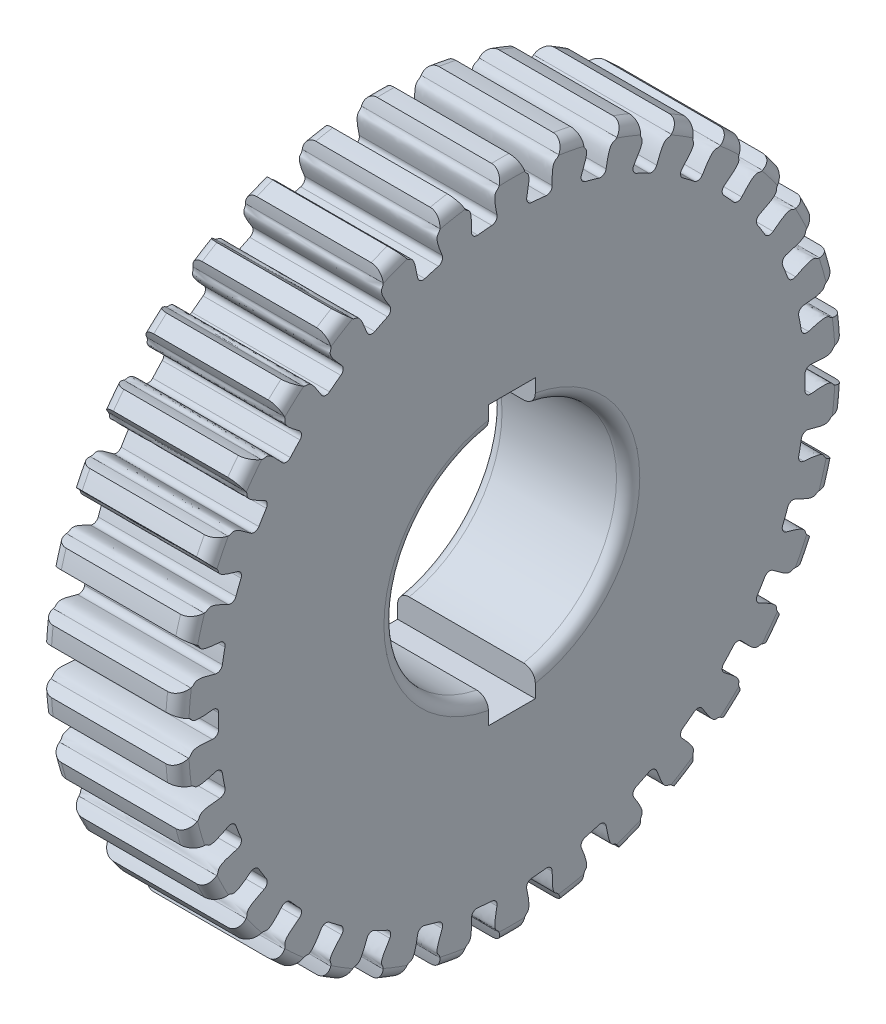
SolidWorks part; units mm, degrees
ref_plane "Front Plane" through (0, 0, 0) normal (0, 0, 1) x (1, 0, 0)
ref_plane "Top Plane" through (0, 0, 0) normal (0, 1, 0) x (1, 0, 0)
ref_plane "Right Plane" through (0, 0, 0) normal (1, 0, 0) x (0, 0, -1)
ref_plane "Plane1" through (4.699, 0, 0) normal (1, 0, 0) x (0, 0, -1)
sketch "Sketch1" plane through (4.699, 0, 0) normal (1, 0, 0) x (0, 0, -1)
  arc A0 (2.7681, 19.8229) -> (0.9216, 19.994) centre (0, 0) ccw
  arc A1 (0.5895, 22.8524) -> (-0.5895, 22.8524) centre (0, 0) ccw
  arc A2 (-0.9214, 19.994) -> (-2.7679, 19.8229) centre (0, 0) ccw
  arc A3 (-3.6196, 22.5716) -> (-4.7786, 22.355) centre (0, 0) ccw
  arc A4 (-4.5796, 19.4842) -> (-6.3632, 18.9768) centre (0, 0) ccw
  arc A5 (-7.7055, 21.5222) -> (-8.805, 21.0963) centre (0, 0) ccw
  arc A6 (-8.0819, 18.311) -> (-9.7419, 17.4844) centre (0, 0) ccw
  arc A7 (-11.529, 19.7398) -> (-12.5315, 19.1192) centre (0, 0) ccw
  arc A8 (-11.3089, 16.5141) -> (-12.7887, 15.3966) centre (0, 0) ccw
  arc A9 (-14.9599, 17.2853) -> (-15.8312, 16.491) centre (0, 0) ccw
  arc A10 (-14.1508, 14.155) -> (-15.4001, 12.7845) centre (0, 0) ccw
  arc A11 (-17.8813, 14.2421) -> (-18.5919, 13.3012) centre (0, 0) ccw
  arc A12 (-16.5108, 11.3137) -> (-17.4871, 9.7371) centre (0, 0) ccw
  arc A13 (-20.1939, 10.7139) -> (-20.7194, 9.6585) centre (0, 0) ccw
  arc A14 (-18.3086, 8.0872) -> (-18.9785, 6.3581) centre (0, 0) ccw
  arc A15 (-21.8187, 6.8209) -> (-22.1414, 5.6868) centre (0, 0) ccw
  arc A16 (-19.4829, 4.5853) -> (-19.8236, 2.7625) centre (0, 0) ccw
  arc A17 (-22.7005, 2.6956) -> (-22.8093, 1.5215) centre (0, 0) ccw
  arc A18 (-19.9937, 0.9273) -> (-19.9937, -0.9271) centre (0, 0) ccw
  arc A19 (-22.8093, -1.5215) -> (-22.7005, -2.6956) centre (0, 0) ccw
  arc A20 (-19.8237, -2.7623) -> (-19.4829, -4.5851) centre (0, 0) ccw
  arc A21 (-22.1414, -5.6868) -> (-21.8187, -6.8209) centre (0, 0) ccw
  arc A22 (-18.9786, -6.3579) -> (-18.3087, -8.0871) centre (0, 0) ccw
  arc A23 (-20.7194, -9.6585) -> (-20.1939, -10.7139) centre (0, 0) ccw
  arc A24 (-17.4872, -9.7369) -> (-16.5109, -11.3136) centre (0, 0) ccw
  arc A25 (-18.5919, -13.3012) -> (-17.8813, -14.2421) centre (0, 0) ccw
  arc A26 (-15.4002, -12.7844) -> (-14.151, -14.1548) centre (0, 0) ccw
  arc A27 (-15.8312, -16.491) -> (-14.9599, -17.2853) centre (0, 0) ccw
  arc A28 (-12.7889, -15.3965) -> (-11.3091, -16.514) centre (0, 0) ccw
  arc A29 (-12.5315, -19.1192) -> (-11.529, -19.7398) centre (0, 0) ccw
  arc A30 (-9.742, -17.4843) -> (-8.0821, -18.3109) centre (0, 0) ccw
  arc A31 (-8.805, -21.0963) -> (-7.7055, -21.5222) centre (0, 0) ccw
  arc A32 (-6.3634, -18.9767) -> (-4.5798, -19.4842) centre (0, 0) ccw
  arc A33 (-4.7786, -22.355) -> (-3.6196, -22.5716) centre (0, 0) ccw
  arc A34 (-2.7681, -19.8229) -> (-0.9216, -19.994) centre (0, 0) ccw
  arc A35 (-0.5895, -22.8524) -> (0.5895, -22.8524) centre (0, 0) ccw
  arc A36 (0.9214, -19.994) -> (2.7679, -19.8229) centre (0, 0) ccw
  arc A37 (3.6196, -22.5716) -> (4.7786, -22.355) centre (0, 0) ccw
  arc A38 (4.5796, -19.4842) -> (6.3632, -18.9768) centre (0, 0) ccw
  arc A39 (7.7055, -21.5222) -> (8.805, -21.0963) centre (0, 0) ccw
  arc A40 (8.0819, -18.311) -> (9.7419, -17.4844) centre (0, 0) ccw
  arc A41 (11.529, -19.7398) -> (12.5315, -19.1192) centre (0, 0) ccw
  arc A42 (11.3089, -16.5141) -> (12.7887, -15.3966) centre (0, 0) ccw
  arc A43 (14.9599, -17.2853) -> (15.8312, -16.491) centre (0, 0) ccw
  arc A44 (14.1508, -14.155) -> (15.4001, -12.7845) centre (0, 0) ccw
  arc A45 (17.8813, -14.2421) -> (18.5919, -13.3012) centre (0, 0) ccw
  arc A46 (16.5108, -11.3137) -> (17.4871, -9.7371) centre (0, 0) ccw
  arc A47 (20.1939, -10.7139) -> (20.7194, -9.6585) centre (0, 0) ccw
  arc A48 (18.3086, -8.0872) -> (18.9785, -6.3581) centre (0, 0) ccw
  arc A49 (21.8187, -6.8209) -> (22.1414, -5.6868) centre (0, 0) ccw
  arc A50 (19.4829, -4.5853) -> (19.8236, -2.7625) centre (0, 0) ccw
  arc A51 (22.7005, -2.6956) -> (22.8093, -1.5215) centre (0, 0) ccw
  arc A52 (19.9937, -0.9273) -> (19.9937, 0.9271) centre (0, 0) ccw
  arc A53 (22.8093, 1.5215) -> (22.7005, 2.6956) centre (0, 0) ccw
  arc A54 (19.8237, 2.7623) -> (19.4829, 4.5851) centre (0, 0) ccw
  arc A55 (22.1414, 5.6868) -> (21.8187, 6.8209) centre (0, 0) ccw
  arc A56 (18.9786, 6.3579) -> (18.3087, 8.0871) centre (0, 0) ccw
  arc A57 (20.7194, 9.6585) -> (20.1939, 10.7139) centre (0, 0) ccw
  arc A58 (17.4872, 9.7369) -> (16.5109, 11.3136) centre (0, 0) ccw
  arc A59 (18.5919, 13.3012) -> (17.8813, 14.2421) centre (0, 0) ccw
  arc A60 (15.4002, 12.7844) -> (14.151, 14.1548) centre (0, 0) ccw
  arc A61 (15.8312, 16.491) -> (14.9599, 17.2853) centre (0, 0) ccw
  arc A62 (12.7889, 15.3965) -> (11.3091, 16.514) centre (0, 0) ccw
  arc A63 (12.5315, 19.1192) -> (11.529, 19.7398) centre (0, 0) ccw
  arc A64 (9.742, 17.4843) -> (8.0821, 18.3109) centre (0, 0) ccw
  arc A65 (8.805, 21.0963) -> (7.7055, 21.5222) centre (0, 0) ccw
  arc A66 (6.3634, 18.9767) -> (4.5798, 19.4842) centre (0, 0) ccw
  arc A67 (4.7786, 22.355) -> (3.6196, 22.5716) centre (0, 0) ccw
  spline S0 degree 3 poles (1.0171, 20.4278) (0.9864, 20.283) (0.9535, 20.1386) (0.9216, 19.994) knots 0 0 0 0 0.000444 0.000444 0.000444 0.000444
  spline S1 degree 3 poles (0.8652, 22.0811) (0.9791, 21.7014) (1.3741, 22.1121) (1.0171, 20.4278) knots 0 0 0 0 1 1 1 1
  spline S2 degree 3 poles (0.8652, 22.0811) (0.8067, 22.2761) (0.74, 22.4689) (0.6667, 22.6589) (0.6417, 22.7237) (0.616, 22.7882) (0.5895, 22.8524) knots 0 0 0 0 0.000611 0.000611 0.000611 0.000819 0.000819 0.000819 0.000819
  spline S3 degree 3 poles (-0.8652, 22.0811) (-0.8118, 22.2592) (-0.7516, 22.4353) (-0.6857, 22.6092) (-0.6549, 22.6908) (-0.6228, 22.7718) (-0.5895, 22.8524) knots 0 0 0 0 0.000558 0.000558 0.000558 0.000819 0.000819 0.000819 0.000819
  spline S4 degree 3 poles (-1.0171, 20.4278) (-1.3741, 22.1121) (-0.9791, 21.7014) (-0.8652, 22.0811) knots 0 0 0 0 1 1 1 1
  spline S5 degree 3 poles (-1.0171, 20.4278) (-0.9864, 20.2829) (-0.9534, 20.1386) (-0.9214, 19.994) knots 0 0 0 0 0.000444 0.000444 0.000444 0.000444
  spline S6 degree 3 poles (-2.7539, 20.2669) (-2.7574, 20.1188) (-2.7632, 19.9709) (-2.7679, 19.8229) knots 0 0 0 0 0.000444 0.000444 0.000444 0.000444
  spline S7 degree 3 poles (-3.2069, 21.8641) (-3.0252, 21.5118) (-2.7124, 21.9881) (-2.7539, 20.2669) knots 0 0 0 0 1 1 1 1
  spline S8 degree 3 poles (-3.2069, 21.8641) (-3.3002, 22.0451) (-3.4012, 22.2223) (-3.5082, 22.3956) (-3.5447, 22.4547) (-3.5818, 22.5134) (-3.6196, 22.5716) knots 0 0 0 0 0.000611 0.000611 0.000611 0.000819 0.000819 0.000819 0.000819
  spline S9 degree 3 poles (-4.9079, 21.5461) (-4.8789, 21.8176) (-4.8345, 22.0877) (-4.7786, 22.355) knots 0.002506 0.002506 0.002506 0.002506 0.003326 0.003326 0.003326 0.003326
  spline S10 degree 3 poles (-4.7533, 19.8931) (-5.4138, 21.4831) (-4.95, 21.152) (-4.9079, 21.5461) knots 0 0 0 0 1 1 1 1
  spline S11 degree 3 poles (-4.7533, 19.8931) (-4.6965, 19.7563) (-4.6376, 19.6205) (-4.5796, 19.4842) knots 0 0 0 0 0.000444 0.000444 0.000444 0.000444
  spline S12 degree 3 poles (-6.431, 19.4158) (-6.4073, 19.2696) (-6.3858, 19.1231) (-6.3632, 18.9768) knots 0 0 0 0 0.000444 0.000444 0.000444 0.000444
  spline S13 degree 3 poles (-7.1698, 20.9025) (-6.9265, 20.5897) (-6.7065, 21.1153) (-6.431, 19.4158) knots 0 0 0 0 1 1 1 1
  spline S14 degree 3 poles (-7.1698, 20.9025) (-7.2947, 21.0632) (-7.4264, 21.2187) (-7.5633, 21.3693) (-7.6101, 21.4208) (-7.6575, 21.4718) (-7.7055, 21.5222) knots 0.001228 0.001228 0.001228 0.001228 0.001836 0.001836 0.001836 0.002044 0.002044 0.002044 0.002044
  spline S15 degree 3 poles (-8.7834, 20.2774) (-8.7979, 20.4626) (-8.8054, 20.6485) (-8.8068, 20.8342) (-8.8075, 20.9216) (-8.8068, 21.0089) (-8.805, 21.0963) knots 0.001119 0.001119 0.001119 0.001119 0.001674 0.001674 0.001674 0.001935 0.001935 0.001935 0.001935
  spline S16 degree 3 poles (-8.3278, 18.681) (-9.2691, 20.1225) (-8.7524, 19.8823) (-8.7834, 20.2774) knots 0 0 0 0 1 1 1 1
  spline S17 degree 3 poles (-8.3278, 18.681) (-8.2468, 18.557) (-8.1639, 18.4343) (-8.0819, 18.311) knots 0 0 0 0 0.000444 0.000444 0.000444 0.000444
  spline S18 degree 3 poles (-9.8891, 17.9035) (-9.839, 17.7642) (-9.7909, 17.6241) (-9.7419, 17.4844) knots 0 0 0 0 0.000444 0.000444 0.000444 0.000444
  spline S19 degree 3 poles (-10.8885, 19.2292) (-10.5919, 18.9664) (-10.4722, 19.5235) (-9.8891, 17.9035) knots 0 0 0 0 1 1 1 1
  spline S20 degree 3 poles (-10.8885, 19.2292) (-11.0409, 19.3642) (-11.1989, 19.4928) (-11.3611, 19.6157) (-11.4166, 19.6577) (-11.4726, 19.6991) (-11.529, 19.7398) knots 0.001228 0.001228 0.001228 0.001228 0.001836 0.001836 0.001836 0.002044 0.002044 0.002044 0.002044
  spline S21 degree 3 poles (-12.3598, 18.3182) (-12.4081, 18.4976) (-12.4496, 18.6789) (-12.4851, 18.8612) (-12.5018, 18.947) (-12.5173, 19.033) (-12.5315, 19.1192) knots 0.001119 0.001119 0.001119 0.001119 0.001674 0.001674 0.001674 0.001935 0.001935 0.001935 0.001935
  spline S22 degree 3 poles (-11.6186, 16.8327) (-12.8088, 18.0767) (-12.2568, 17.9355) (-12.3598, 18.3182) knots 0 0 0 0 1 1 1 1
  spline S23 degree 3 poles (-11.6186, 16.8327) (-11.5162, 16.7257) (-11.4122, 16.6203) (-11.3089, 16.5141) knots 0 0 0 0 0.000444 0.000444 0.000444 0.000444
  spline S24 degree 3 poles (-13.0105, 15.7815) (-12.9356, 15.6538) (-12.8626, 15.525) (-12.7887, 15.3966) knots 0 0 0 0 0.000444 0.000444 0.000444 0.000444
  spline S25 degree 3 poles (-14.2365, 16.901) (-13.8966, 16.6972) (-13.8814, 17.2668) (-13.0105, 15.7815) knots 0 0 0 0 1 1 1 1
  spline S26 degree 3 poles (-14.2365, 16.901) (-14.411, 17.0057) (-14.59, 17.1031) (-14.7721, 17.1941) (-14.8343, 17.2252) (-14.8969, 17.2556) (-14.9599, 17.2853) knots 0.001228 0.001228 0.001228 0.001228 0.001836 0.001836 0.001836 0.002044 0.002044 0.002044 0.002044
  spline S27 degree 3 poles (-15.5153, 15.7352) (-15.5958, 15.9026) (-15.6699, 16.0733) (-15.7383, 16.246) (-15.7705, 16.3272) (-15.8014, 16.4089) (-15.8312, 16.491) knots 0.001119 0.001119 0.001119 0.001119 0.001674 0.001674 0.001674 0.001935 0.001935 0.001935 0.001935
  spline S28 degree 3 poles (-14.5137, 14.4111) (-15.9123, 15.4153) (-15.3437, 15.378) (-15.5153, 15.7352) knots 0 0 0 0 1 1 1 1
  spline S29 degree 3 poles (-14.5137, 14.4111) (-14.3935, 14.3248) (-14.2718, 14.2403) (-14.1508, 14.155) knots 0 0 0 0 0.000444 0.000444 0.000444 0.000444
  spline S30 degree 3 poles (-15.6888, 13.1221) (-15.5917, 13.0103) (-15.4963, 12.8971) (-15.4001, 12.7845) knots 0 0 0 0 0.000444 0.000444 0.000444 0.000444
  spline S31 degree 3 poles (-17.0996, 13.9973) (-16.7281, 13.8594) (-16.8178, 14.4221) (-15.6888, 13.1221) knots 0 0 0 0 1 1 1 1
  spline S32 degree 3 poles (-17.0996, 13.9973) (-17.2904, 14.0681) (-17.4843, 14.131) (-17.6799, 14.187) (-17.7469, 14.2061) (-17.814, 14.2245) (-17.8813, 14.2421) knots 0.001228 0.001228 0.001228 0.001228 0.001836 0.001836 0.001836 0.002044 0.002044 0.002044 0.002044
  spline S33 degree 3 poles (-18.1425, 12.6163) (-18.2523, 12.7661) (-18.3565, 12.9202) (-18.4555, 13.0774) (-18.5021, 13.1513) (-18.5475, 13.226) (-18.5919, 13.3012) knots 0.001119 0.001119 0.001119 0.001119 0.001674 0.001674 0.001674 0.001935 0.001935 0.001935 0.001935
  spline S34 degree 3 poles (-16.9147, 11.4989) (-18.4739, 12.229) (-17.9081, 12.2967) (-18.1425, 12.6163) knots 0 0 0 0 1 1 1 1
  spline S35 degree 3 poles (-16.9147, 11.4989) (-16.7805, 11.4361) (-16.6455, 11.3754) (-16.5108, 11.3137) knots 0 0 0 0 0.000444 0.000444 0.000444 0.000444
  spline S36 degree 3 poles (-17.8329, 10.0159) (-17.7169, 9.9238) (-17.6023, 9.8301) (-17.4871, 9.7371) knots 0 0 0 0 0.000444 0.000444 0.000444 0.000444
  spline S37 degree 3 poles (-19.3805, 10.6169) (-18.9899, 10.5496) (-19.1815, 11.0863) (-17.8329, 10.0159) knots 0 0 0 0 1 1 1 1
  spline S38 degree 3 poles (-19.3805, 10.6169) (-19.581, 10.6515) (-19.7832, 10.6777) (-19.9858, 10.6967) (-20.0551, 10.7033) (-20.1244, 10.709) (-20.1939, 10.7139) knots 0.001228 0.001228 0.001228 0.001228 0.001836 0.001836 0.001836 0.002044 0.002044 0.002044 0.002044
  spline S39 degree 3 poles (-20.1518, 9.0678) (-20.2873, 9.1949) (-20.418, 9.3273) (-20.5442, 9.4636) (-20.6036, 9.5277) (-20.662, 9.5927) (-20.7194, 9.6585) knots 0.001119 0.001119 0.001119 0.001119 0.001674 0.001674 0.001674 0.001935 0.001935 0.001935 0.001935
  spline S40 degree 3 poles (-18.7396, 8.195) (-20.4064, 8.6262) (-19.8627, 8.7967) (-20.1518, 9.0678) knots 0 0 0 0 1 1 1 1
  spline S41 degree 3 poles (-18.7396, 8.195) (-18.5962, 8.1579) (-18.4523, 8.1231) (-18.3086, 8.0872) knots 0 0 0 0 0.000444 0.000444 0.000444 0.000444
  spline S42 degree 3 poles (-19.3697, 6.5686) (-19.2387, 6.4994) (-19.1088, 6.4283) (-18.9785, 6.3581) knots 0 0 0 0 0.000444 0.000444 0.000444 0.000444
  spline S43 degree 3 poles (-21.0013, 6.875) (-20.6051, 6.8806) (-20.892, 7.3729) (-19.3697, 6.5686) knots 0 0 0 0 1 1 1 1
  spline S44 degree 3 poles (-21.0013, 6.875) (-21.2048, 6.8721) (-21.4083, 6.8607) (-21.611, 6.8422) (-21.6803, 6.8359) (-21.7495, 6.8288) (-21.8187, 6.8209) knots 0.001228 0.001228 0.001228 0.001228 0.001836 0.001836 0.001836 0.002044 0.002044 0.002044 0.002044
  spline S45 degree 3 poles (-21.4749, 5.2106) (-21.6315, 5.3106) (-21.7843, 5.4166) (-21.9334, 5.5274) (-22.0035, 5.5795) (-22.0728, 5.6327) (-22.1414, 5.6868) knots 0.001119 0.001119 0.001119 0.001119 0.001674 0.001674 0.001674 0.001935 0.001935 0.001935 0.001935
  spline S46 degree 3 poles (-19.9263, 4.6121) (-21.644, 4.7296) (-21.1409, 4.9972) (-21.4749, 5.2106) knots 0 0 0 0 1 1 1 1
  spline S47 degree 3 poles (-19.9263, 4.6121) (-19.7786, 4.602) (-19.6307, 4.5942) (-19.4829, 4.5853) knots 0 0 0 0 0.000444 0.000444 0.000444 0.000444
  spline S48 degree 3 poles (-20.2468, 2.8976) (-20.1054, 2.8536) (-19.9647, 2.8076) (-19.8236, 2.7625) knots 0 0 0 0 0.000444 0.000444 0.000444 0.000444
  spline S49 degree 3 poles (-21.907, 2.8989) (-21.5185, 2.9773) (-21.891, 3.4085) (-20.2468, 2.8976) knots 0 0 0 0 1 1 1 1
  spline S50 degree 3 poles (-21.907, 2.8989) (-22.1067, 2.8587) (-22.3048, 2.81) (-22.5008, 2.7546) (-22.5676, 2.7357) (-22.6342, 2.716) (-22.7005, 2.6956) knots 0 0 0 0 0.000611 0.000611 0.000611 0.000819 0.000819 0.000819 0.000819
  spline S51 degree 3 poles (-22.0667, 1.1758) (-22.2391, 1.2454) (-22.409, 1.3217) (-22.5761, 1.4033) (-22.6544, 1.4416) (-22.7321, 1.481) (-22.8093, 1.5215) knots 0 0 0 0 0.000558 0.000558 0.000558 0.000819 0.000819 0.000819 0.000819
  spline S52 degree 3 poles (-20.4345, 0.8721) (-22.1446, 0.672) (-21.6992, 1.0275) (-22.0667, 1.1758) knots 0 0 0 0 1 1 1 1
  spline S53 degree 3 poles (-20.4345, 0.8721) (-20.2874, 0.8893) (-20.1406, 0.9088) (-19.9937, 0.9273) knots 0 0 0 0 0.000444 0.000444 0.000444 0.000444
  spline S54 degree 3 poles (-20.4345, -0.8721) (-20.2874, -0.8893) (-20.1406, -0.9087) (-19.9937, -0.9271) knots 0 0 0 0 0.000444 0.000444 0.000444 0.000444
  spline S55 degree 3 poles (-22.0667, -1.1758) (-21.6992, -1.0275) (-22.1446, -0.672) (-20.4345, -0.8721) knots 0 0 0 0 1 1 1 1
  spline S56 degree 3 poles (-22.0667, -1.1758) (-22.2556, -1.2521) (-22.4413, -1.3363) (-22.6238, -1.4268) (-22.686, -1.4577) (-22.7478, -1.4893) (-22.8093, -1.5215) knots 0 0 0 0 0.000611 0.000611 0.000611 0.000819 0.000819 0.000819 0.000819
  spline S57 degree 3 poles (-21.907, -2.8989) (-22.1747, -2.845) (-22.4396, -2.7759) (-22.7005, -2.6956) knots 0.002506 0.002506 0.002506 0.002506 0.003326 0.003326 0.003326 0.003326
  spline S58 degree 3 poles (-20.2468, -2.8976) (-21.891, -3.4085) (-21.5185, -2.9773) (-21.907, -2.8989) knots 0 0 0 0 1 1 1 1
  spline S59 degree 3 poles (-20.2468, -2.8976) (-20.1054, -2.8536) (-19.9647, -2.8075) (-19.8237, -2.7623) knots 0 0 0 0 0.000444 0.000444 0.000444 0.000444
  spline S60 degree 3 poles (-19.9263, -4.6121) (-19.7786, -4.602) (-19.6307, -4.5941) (-19.4829, -4.5851) knots 0 0 0 0 0.000444 0.000444 0.000444 0.000444
  spline S61 degree 3 poles (-21.4749, -5.2106) (-21.1409, -4.9972) (-21.644, -4.7296) (-19.9263, -4.6121) knots 0 0 0 0 1 1 1 1
  spline S62 degree 3 poles (-21.4749, -5.2106) (-21.6464, -5.3201) (-21.8134, -5.4369) (-21.976, -5.5593) (-22.0316, -5.6012) (-22.0867, -5.6437) (-22.1414, -5.6868) knots 0.001228 0.001228 0.001228 0.001228 0.001836 0.001836 0.001836 0.002044 0.002044 0.002044 0.002044
  spline S63 degree 3 poles (-21.0013, -6.875) (-21.1871, -6.8724) (-21.3728, -6.8626) (-21.5579, -6.8469) (-21.645, -6.8395) (-21.7319, -6.8308) (-21.8187, -6.8209) knots 0.001119 0.001119 0.001119 0.001119 0.001674 0.001674 0.001674 0.001935 0.001935 0.001935 0.001935
  spline S64 degree 3 poles (-19.3697, -6.5686) (-20.892, -7.3729) (-20.6051, -6.8806) (-21.0013, -6.875) knots 0 0 0 0 1 1 1 1
  spline S65 degree 3 poles (-19.3697, -6.5686) (-19.2387, -6.4994) (-19.1089, -6.4282) (-18.9786, -6.3579) knots 0 0 0 0 0.000444 0.000444 0.000444 0.000444
  spline S66 degree 3 poles (-18.7396, -8.195) (-18.5962, -8.1579) (-18.4523, -8.123) (-18.3087, -8.0871) knots 0 0 0 0 0.000444 0.000444 0.000444 0.000444
  spline S67 degree 3 poles (-20.1518, -9.0678) (-19.8627, -8.7967) (-20.4064, -8.6262) (-18.7396, -8.195) knots 0 0 0 0 1 1 1 1
  spline S68 degree 3 poles (-20.1518, -9.0678) (-20.3003, -9.2071) (-20.443, -9.3526) (-20.5803, -9.5028) (-20.6273, -9.5541) (-20.6736, -9.606) (-20.7194, -9.6585) knots 0.001228 0.001228 0.001228 0.001228 0.001836 0.001836 0.001836 0.002044 0.002044 0.002044 0.002044
  spline S69 degree 3 poles (-19.3805, -10.6169) (-19.5636, -10.6485) (-19.7479, -10.673) (-19.9328, -10.6916) (-20.0197, -10.7003) (-20.1067, -10.7077) (-20.1939, -10.7139) knots 0.001119 0.001119 0.001119 0.001119 0.001674 0.001674 0.001674 0.001935 0.001935 0.001935 0.001935
  spline S70 degree 3 poles (-17.8329, -10.0159) (-19.1815, -11.0863) (-18.9899, -10.5496) (-19.3805, -10.6169) knots 0 0 0 0 1 1 1 1
  spline S71 degree 3 poles (-17.8329, -10.0159) (-17.7169, -9.9238) (-17.6023, -9.83) (-17.4872, -9.7369) knots 0 0 0 0 0.000444 0.000444 0.000444 0.000444
  spline S72 degree 3 poles (-16.9147, -11.4989) (-16.7806, -11.4361) (-16.6455, -11.3753) (-16.5109, -11.3136) knots 0 0 0 0 0.000444 0.000444 0.000444 0.000444
  spline S73 degree 3 poles (-18.1425, -12.6163) (-17.9081, -12.2967) (-18.4739, -12.229) (-16.9147, -11.4989) knots 0 0 0 0 1 1 1 1
  spline S74 degree 3 poles (-18.1425, -12.6163) (-18.2628, -12.7804) (-18.3763, -12.9497) (-18.4837, -13.1226) (-18.5205, -13.1817) (-18.5565, -13.2412) (-18.5919, -13.3012) knots 0.001228 0.001228 0.001228 0.001228 0.001836 0.001836 0.001836 0.002044 0.002044 0.002044 0.002044
  spline S75 degree 3 poles (-17.0996, -13.9973) (-17.2738, -14.0619) (-17.4505, -14.12) (-17.6288, -14.1722) (-17.7126, -14.1967) (-17.7968, -14.22) (-17.8813, -14.2421) knots 0.001119 0.001119 0.001119 0.001119 0.001674 0.001674 0.001674 0.001935 0.001935 0.001935 0.001935
  spline S76 degree 3 poles (-15.6888, -13.1221) (-16.8178, -14.4221) (-16.7281, -13.8594) (-17.0996, -13.9973) knots 0 0 0 0 1 1 1 1
  spline S77 degree 3 poles (-15.6888, -13.1221) (-15.5917, -13.0103) (-15.4964, -12.897) (-15.4002, -12.7844) knots 0 0 0 0 0.000444 0.000444 0.000444 0.000444
  spline S78 degree 3 poles (-14.5137, -14.4111) (-14.3935, -14.3248) (-14.2719, -14.2402) (-14.151, -14.1548) knots 0 0 0 0 0.000444 0.000444 0.000444 0.000444
  spline S79 degree 3 poles (-15.5153, -15.7352) (-15.3437, -15.378) (-15.9123, -15.4153) (-14.5137, -14.4111) knots 0 0 0 0 1 1 1 1
  spline S80 degree 3 poles (-15.5153, -15.7352) (-15.6035, -15.9186) (-15.684, -16.1059) (-15.7578, -16.2955) (-15.783, -16.3604) (-15.8075, -16.4255) (-15.8312, -16.491) knots 0.001228 0.001228 0.001228 0.001228 0.001836 0.001836 0.001836 0.002044 0.002044 0.002044 0.002044
  spline S81 degree 3 poles (-14.2365, -16.901) (-14.3958, -16.9966) (-14.5589, -17.0861) (-14.7245, -17.1702) (-14.8024, -17.2097) (-14.8809, -17.248) (-14.9599, -17.2853) knots 0.001119 0.001119 0.001119 0.001119 0.001674 0.001674 0.001674 0.001935 0.001935 0.001935 0.001935
  spline S82 degree 3 poles (-13.0105, -15.7815) (-13.8814, -17.2668) (-13.8966, -16.6972) (-14.2365, -16.901) knots 0 0 0 0 1 1 1 1
  spline S83 degree 3 poles (-13.0105, -15.7815) (-12.9356, -15.6538) (-12.8627, -15.5249) (-12.7889, -15.3965) knots 0 0 0 0 0.000444 0.000444 0.000444 0.000444
  spline S84 degree 3 poles (-11.6186, -16.8327) (-11.5162, -16.7257) (-11.4123, -16.6202) (-11.3091, -16.514) knots 0 0 0 0 0.000444 0.000444 0.000444 0.000444
  spline S85 degree 3 poles (-12.3598, -18.3182) (-12.2568, -17.9355) (-12.8088, -18.0767) (-11.6186, -16.8327) knots 0 0 0 0 1 1 1 1
  spline S86 degree 3 poles (-12.3598, -18.3182) (-12.4127, -18.5147) (-12.4575, -18.7135) (-12.4952, -18.9135) (-12.5081, -18.9819) (-12.5201, -19.0505) (-12.5315, -19.1192) knots 0.001228 0.001228 0.001228 0.001228 0.001836 0.001836 0.001836 0.002044 0.002044 0.002044 0.002044
  spline S87 degree 3 poles (-10.8885, -19.2292) (-11.0276, -19.3524) (-11.1714, -19.4703) (-11.3188, -19.5834) (-11.3881, -19.6366) (-11.4582, -19.6887) (-11.529, -19.7398) knots 0.001119 0.001119 0.001119 0.001119 0.001674 0.001674 0.001674 0.001935 0.001935 0.001935 0.001935
  spline S88 degree 3 poles (-9.8891, -17.9035) (-10.4722, -19.5235) (-10.5919, -18.9663) (-10.8885, -19.2292) knots 0 0 0 0 1 1 1 1
  spline S89 degree 3 poles (-9.8891, -17.9035) (-9.839, -17.7642) (-9.791, -17.6241) (-9.742, -17.4843) knots 0 0 0 0 0.000444 0.000444 0.000444 0.000444
  spline S90 degree 3 poles (-8.3278, -18.681) (-8.2468, -18.557) (-8.164, -18.4342) (-8.0821, -18.3109) knots 0 0 0 0 0.000444 0.000444 0.000444 0.000444
  spline S91 degree 3 poles (-8.7834, -20.2774) (-8.7524, -19.8823) (-9.2691, -20.1225) (-8.3278, -18.681) knots 0 0 0 0 1 1 1 1
  spline S92 degree 3 poles (-8.7834, -20.2774) (-8.7993, -20.4803) (-8.8067, -20.684) (-8.8071, -20.8875) (-8.8072, -20.9571) (-8.8065, -21.0267) (-8.805, -21.0963) knots 0.001228 0.001228 0.001228 0.001228 0.001836 0.001836 0.001836 0.002044 0.002044 0.002044 0.002044
  spline S93 degree 3 poles (-7.1698, -20.9025) (-7.2838, -21.0492) (-7.4035, -21.1915) (-7.5276, -21.3298) (-7.586, -21.3948) (-7.6453, -21.4589) (-7.7055, -21.5222) knots 0.001119 0.001119 0.001119 0.001119 0.001674 0.001674 0.001674 0.001935 0.001935 0.001935 0.001935
  spline S94 degree 3 poles (-6.431, -19.4158) (-6.7065, -21.1153) (-6.9265, -20.5897) (-7.1698, -20.9025) knots 0 0 0 0 1 1 1 1
  spline S95 degree 3 poles (-6.431, -19.4158) (-6.4073, -19.2696) (-6.3859, -19.1231) (-6.3634, -18.9767) knots 0 0 0 0 0.000444 0.000444 0.000444 0.000444
  spline S96 degree 3 poles (-4.7533, -19.8931) (-4.6965, -19.7564) (-4.6377, -19.6205) (-4.5798, -19.4842) knots 0 0 0 0 0.000444 0.000444 0.000444 0.000444
  spline S97 degree 3 poles (-4.9079, -21.5461) (-4.95, -21.152) (-5.4138, -21.4831) (-4.7533, -19.8931) knots 0 0 0 0 1 1 1 1
  spline S98 degree 3 poles (-4.9079, -21.5461) (-4.8863, -21.7484) (-4.8561, -21.95) (-4.819, -22.1501) (-4.8064, -22.2185) (-4.7929, -22.2868) (-4.7786, -22.355) knots 0.001228 0.001228 0.001228 0.001228 0.001836 0.001836 0.001836 0.002044 0.002044 0.002044 0.002044
  spline S99 degree 3 poles (-3.2069, -21.8641) (-3.292, -22.0292) (-3.3835, -22.1911) (-3.4801, -22.3498) (-3.5255, -22.4244) (-3.5721, -22.4984) (-3.6196, -22.5716) knots 0.001119 0.001119 0.001119 0.001119 0.001674 0.001674 0.001674 0.001935 0.001935 0.001935 0.001935
  spline S100 degree 3 poles (-2.7539, -20.2669) (-2.7124, -21.9881) (-3.0252, -21.5118) (-3.2069, -21.8641) knots 0 0 0 0 1 1 1 1
  spline S101 degree 3 poles (-2.7539, -20.2669) (-2.7574, -20.1188) (-2.7633, -19.9709) (-2.7681, -19.8229) knots 0 0 0 0 0.000444 0.000444 0.000444 0.000444
  spline S102 degree 3 poles (-1.0171, -20.4278) (-0.9864, -20.283) (-0.9535, -20.1386) (-0.9216, -19.994) knots 0 0 0 0 0.000444 0.000444 0.000444 0.000444
  spline S103 degree 3 poles (-0.8652, -22.0811) (-0.9791, -21.7014) (-1.3741, -22.1121) (-1.0171, -20.4278) knots 0 0 0 0 1 1 1 1
  spline S104 degree 3 poles (-0.8652, -22.0811) (-0.8067, -22.2761) (-0.74, -22.4689) (-0.6667, -22.6589) (-0.6417, -22.7237) (-0.616, -22.7882) (-0.5895, -22.8524) knots 0 0 0 0 0.000611 0.000611 0.000611 0.000819 0.000819 0.000819 0.000819
  spline S105 degree 3 poles (0.8652, -22.0811) (0.8118, -22.2592) (0.7516, -22.4353) (0.6857, -22.6093) (0.6549, -22.6908) (0.6228, -22.7718) (0.5895, -22.8524) knots 0 0 0 0 0.000558 0.000558 0.000558 0.000819 0.000819 0.000819 0.000819
  spline S106 degree 3 poles (1.0171, -20.4278) (1.3741, -22.1121) (0.9791, -21.7014) (0.8652, -22.0811) knots 0 0 0 0 1 1 1 1
  spline S107 degree 3 poles (1.0171, -20.4278) (0.9864, -20.2829) (0.9534, -20.1386) (0.9214, -19.994) knots 0 0 0 0 0.000444 0.000444 0.000444 0.000444
  spline S108 degree 3 poles (2.7539, -20.2669) (2.7574, -20.1188) (2.7632, -19.9709) (2.7679, -19.8229) knots 0 0 0 0 0.000444 0.000444 0.000444 0.000444
  spline S109 degree 3 poles (3.2069, -21.8641) (3.0252, -21.5118) (2.7124, -21.9881) (2.7539, -20.2669) knots 0 0 0 0 1 1 1 1
  spline S110 degree 3 poles (3.2069, -21.8641) (3.3002, -22.0451) (3.4012, -22.2223) (3.5082, -22.3956) (3.5447, -22.4547) (3.5818, -22.5134) (3.6196, -22.5716) knots 0 0 0 0 0.000611 0.000611 0.000611 0.000819 0.000819 0.000819 0.000819
  spline S111 degree 3 poles (4.9079, -21.5461) (4.8789, -21.8176) (4.8345, -22.0877) (4.7786, -22.355) knots 0.002506 0.002506 0.002506 0.002506 0.003326 0.003326 0.003326 0.003326
  spline S112 degree 3 poles (4.7533, -19.8931) (5.4138, -21.4831) (4.95, -21.152) (4.9079, -21.5461) knots 0 0 0 0 1 1 1 1
  spline S113 degree 3 poles (4.7533, -19.8931) (4.6965, -19.7563) (4.6376, -19.6205) (4.5796, -19.4842) knots 0 0 0 0 0.000444 0.000444 0.000444 0.000444
  spline S114 degree 3 poles (6.431, -19.4158) (6.4073, -19.2696) (6.3858, -19.1231) (6.3632, -18.9768) knots 0 0 0 0 0.000444 0.000444 0.000444 0.000444
  spline S115 degree 3 poles (7.1698, -20.9025) (6.9265, -20.5897) (6.7065, -21.1153) (6.431, -19.4158) knots 0 0 0 0 1 1 1 1
  spline S116 degree 3 poles (7.1698, -20.9025) (7.2947, -21.0632) (7.4264, -21.2187) (7.5633, -21.3693) (7.6101, -21.4208) (7.6575, -21.4718) (7.7055, -21.5222) knots 0.001228 0.001228 0.001228 0.001228 0.001836 0.001836 0.001836 0.002044 0.002044 0.002044 0.002044
  spline S117 degree 3 poles (8.7834, -20.2774) (8.7979, -20.4626) (8.8054, -20.6485) (8.8068, -20.8342) (8.8075, -20.9216) (8.8068, -21.0089) (8.805, -21.0963) knots 0.001119 0.001119 0.001119 0.001119 0.001674 0.001674 0.001674 0.001935 0.001935 0.001935 0.001935
  spline S118 degree 3 poles (8.3278, -18.681) (9.2691, -20.1225) (8.7524, -19.8823) (8.7834, -20.2774) knots 0 0 0 0 1 1 1 1
  spline S119 degree 3 poles (8.3278, -18.681) (8.2468, -18.557) (8.1639, -18.4343) (8.0819, -18.311) knots 0 0 0 0 0.000444 0.000444 0.000444 0.000444
  spline S120 degree 3 poles (9.8891, -17.9035) (9.839, -17.7642) (9.7909, -17.6241) (9.7419, -17.4844) knots 0 0 0 0 0.000444 0.000444 0.000444 0.000444
  spline S121 degree 3 poles (10.8885, -19.2292) (10.5919, -18.9663) (10.4722, -19.5235) (9.8891, -17.9035) knots 0 0 0 0 1 1 1 1
  spline S122 degree 3 poles (10.8885, -19.2292) (11.0408, -19.3641) (11.1989, -19.4928) (11.3611, -19.6157) (11.4166, -19.6577) (11.4726, -19.6991) (11.529, -19.7398) knots 0.001228 0.001228 0.001228 0.001228 0.001836 0.001836 0.001836 0.002044 0.002044 0.002044 0.002044
  spline S123 degree 3 poles (12.3598, -18.3182) (12.4081, -18.4976) (12.4496, -18.6789) (12.4851, -18.8612) (12.5018, -18.947) (12.5173, -19.033) (12.5315, -19.1192) knots 0.001119 0.001119 0.001119 0.001119 0.001674 0.001674 0.001674 0.001935 0.001935 0.001935 0.001935
  spline S124 degree 3 poles (11.6186, -16.8327) (12.8088, -18.0767) (12.2568, -17.9355) (12.3598, -18.3182) knots 0 0 0 0 1 1 1 1
  spline S125 degree 3 poles (11.6186, -16.8327) (11.5162, -16.7257) (11.4122, -16.6203) (11.3089, -16.5141) knots 0 0 0 0 0.000444 0.000444 0.000444 0.000444
  spline S126 degree 3 poles (13.0105, -15.7815) (12.9356, -15.6538) (12.8626, -15.525) (12.7887, -15.3966) knots 0 0 0 0 0.000444 0.000444 0.000444 0.000444
  spline S127 degree 3 poles (14.2365, -16.901) (13.8966, -16.6972) (13.8814, -17.2668) (13.0105, -15.7815) knots 0 0 0 0 1 1 1 1
  spline S128 degree 3 poles (14.2365, -16.901) (14.411, -17.0057) (14.59, -17.1031) (14.7721, -17.1941) (14.8343, -17.2252) (14.8969, -17.2556) (14.9599, -17.2853) knots 0.001228 0.001228 0.001228 0.001228 0.001836 0.001836 0.001836 0.002044 0.002044 0.002044 0.002044
  spline S129 degree 3 poles (15.5153, -15.7352) (15.5958, -15.9026) (15.6699, -16.0733) (15.7383, -16.246) (15.7705, -16.3272) (15.8014, -16.4089) (15.8312, -16.491) knots 0.001119 0.001119 0.001119 0.001119 0.001674 0.001674 0.001674 0.001935 0.001935 0.001935 0.001935
  spline S130 degree 3 poles (14.5137, -14.4111) (15.9123, -15.4153) (15.3437, -15.378) (15.5153, -15.7352) knots 0 0 0 0 1 1 1 1
  spline S131 degree 3 poles (14.5137, -14.4111) (14.3935, -14.3248) (14.2718, -14.2403) (14.1508, -14.155) knots 0 0 0 0 0.000444 0.000444 0.000444 0.000444
  spline S132 degree 3 poles (15.6888, -13.1221) (15.5917, -13.0103) (15.4963, -12.8971) (15.4001, -12.7845) knots 0 0 0 0 0.000444 0.000444 0.000444 0.000444
  spline S133 degree 3 poles (17.0996, -13.9973) (16.7281, -13.8594) (16.8178, -14.4221) (15.6888, -13.1221) knots 0 0 0 0 1 1 1 1
  spline S134 degree 3 poles (17.0996, -13.9973) (17.2904, -14.0681) (17.4843, -14.131) (17.6799, -14.187) (17.7469, -14.2061) (17.814, -14.2245) (17.8813, -14.2421) knots 0.001228 0.001228 0.001228 0.001228 0.001836 0.001836 0.001836 0.002044 0.002044 0.002044 0.002044
  spline S135 degree 3 poles (18.1425, -12.6163) (18.2523, -12.7661) (18.3565, -12.9202) (18.4555, -13.0774) (18.5021, -13.1513) (18.5475, -13.226) (18.5919, -13.3012) knots 0.001119 0.001119 0.001119 0.001119 0.001674 0.001674 0.001674 0.001935 0.001935 0.001935 0.001935
  spline S136 degree 3 poles (16.9147, -11.4989) (18.4739, -12.229) (17.9081, -12.2967) (18.1425, -12.6163) knots 0 0 0 0 1 1 1 1
  spline S137 degree 3 poles (16.9147, -11.4989) (16.7805, -11.4361) (16.6455, -11.3754) (16.5108, -11.3137) knots 0 0 0 0 0.000444 0.000444 0.000444 0.000444
  spline S138 degree 3 poles (17.8329, -10.0159) (17.7169, -9.9238) (17.6023, -9.8301) (17.4871, -9.7371) knots 0 0 0 0 0.000444 0.000444 0.000444 0.000444
  spline S139 degree 3 poles (19.3805, -10.6169) (18.9899, -10.5496) (19.1815, -11.0863) (17.8329, -10.0159) knots 0 0 0 0 1 1 1 1
  spline S140 degree 3 poles (19.3805, -10.6169) (19.581, -10.6515) (19.7831, -10.6776) (19.9858, -10.6967) (20.055, -10.7033) (20.1244, -10.709) (20.1939, -10.7139) knots 0.001228 0.001228 0.001228 0.001228 0.001836 0.001836 0.001836 0.002044 0.002044 0.002044 0.002044
  spline S141 degree 3 poles (20.1518, -9.0678) (20.2873, -9.1949) (20.418, -9.3273) (20.5442, -9.4636) (20.6036, -9.5277) (20.662, -9.5927) (20.7194, -9.6585) knots 0.001119 0.001119 0.001119 0.001119 0.001674 0.001674 0.001674 0.001935 0.001935 0.001935 0.001935
  spline S142 degree 3 poles (18.7396, -8.195) (20.4064, -8.6262) (19.8627, -8.7967) (20.1518, -9.0678) knots 0 0 0 0 1 1 1 1
  spline S143 degree 3 poles (18.7396, -8.195) (18.5962, -8.1579) (18.4523, -8.1231) (18.3086, -8.0872) knots 0 0 0 0 0.000444 0.000444 0.000444 0.000444
  spline S144 degree 3 poles (19.3697, -6.5686) (19.2387, -6.4994) (19.1088, -6.4283) (18.9785, -6.3581) knots 0 0 0 0 0.000444 0.000444 0.000444 0.000444
  spline S145 degree 3 poles (21.0013, -6.875) (20.6051, -6.8806) (20.892, -7.3729) (19.3697, -6.5686) knots 0 0 0 0 1 1 1 1
  spline S146 degree 3 poles (21.0013, -6.875) (21.2048, -6.8721) (21.4083, -6.8607) (21.611, -6.8422) (21.6803, -6.8359) (21.7495, -6.8288) (21.8187, -6.8209) knots 0.001228 0.001228 0.001228 0.001228 0.001836 0.001836 0.001836 0.002044 0.002044 0.002044 0.002044
  spline S147 degree 3 poles (21.4749, -5.2106) (21.6315, -5.3106) (21.7843, -5.4166) (21.9334, -5.5274) (22.0035, -5.5795) (22.0728, -5.6327) (22.1414, -5.6868) knots 0.001119 0.001119 0.001119 0.001119 0.001674 0.001674 0.001674 0.001935 0.001935 0.001935 0.001935
  spline S148 degree 3 poles (19.9263, -4.6121) (21.644, -4.7296) (21.1409, -4.9972) (21.4749, -5.2106) knots 0 0 0 0 1 1 1 1
  spline S149 degree 3 poles (19.9263, -4.6121) (19.7786, -4.602) (19.6307, -4.5942) (19.4829, -4.5853) knots 0 0 0 0 0.000444 0.000444 0.000444 0.000444
  spline S150 degree 3 poles (20.2468, -2.8976) (20.1054, -2.8536) (19.9647, -2.8076) (19.8236, -2.7625) knots 0 0 0 0 0.000444 0.000444 0.000444 0.000444
  spline S151 degree 3 poles (21.907, -2.8989) (21.5185, -2.9773) (21.891, -3.4085) (20.2468, -2.8976) knots 0 0 0 0 1 1 1 1
  spline S152 degree 3 poles (21.907, -2.8989) (22.1067, -2.8587) (22.3048, -2.81) (22.5008, -2.7546) (22.5676, -2.7357) (22.6342, -2.716) (22.7005, -2.6956) knots 0 0 0 0 0.000611 0.000611 0.000611 0.000819 0.000819 0.000819 0.000819
  spline S153 degree 3 poles (22.0667, -1.1758) (22.2391, -1.2454) (22.409, -1.3217) (22.5761, -1.4033) (22.6544, -1.4416) (22.7321, -1.481) (22.8093, -1.5215) knots 0 0 0 0 0.000558 0.000558 0.000558 0.000819 0.000819 0.000819 0.000819
  spline S154 degree 3 poles (20.4345, -0.8721) (22.1446, -0.672) (21.6992, -1.0275) (22.0667, -1.1758) knots 0 0 0 0 1 1 1 1
  spline S155 degree 3 poles (20.4345, -0.8721) (20.2874, -0.8893) (20.1406, -0.9088) (19.9937, -0.9273) knots 0 0 0 0 0.000444 0.000444 0.000444 0.000444
  spline S156 degree 3 poles (20.4345, 0.8721) (20.2874, 0.8893) (20.1406, 0.9087) (19.9937, 0.9271) knots 0 0 0 0 0.000444 0.000444 0.000444 0.000444
  spline S157 degree 3 poles (22.0667, 1.1758) (21.6992, 1.0275) (22.1446, 0.672) (20.4345, 0.8721) knots 0 0 0 0 1 1 1 1
  spline S158 degree 3 poles (22.0667, 1.1758) (22.2556, 1.2521) (22.4413, 1.3363) (22.6238, 1.4268) (22.686, 1.4577) (22.7478, 1.4893) (22.8093, 1.5215) knots 0 0 0 0 0.000611 0.000611 0.000611 0.000819 0.000819 0.000819 0.000819
  spline S159 degree 3 poles (21.907, 2.8989) (22.1747, 2.845) (22.4396, 2.7759) (22.7005, 2.6956) knots 0.002506 0.002506 0.002506 0.002506 0.003326 0.003326 0.003326 0.003326
  spline S160 degree 3 poles (20.2468, 2.8976) (21.891, 3.4085) (21.5185, 2.9773) (21.907, 2.8989) knots 0 0 0 0 1 1 1 1
  spline S161 degree 3 poles (20.2468, 2.8976) (20.1054, 2.8536) (19.9647, 2.8075) (19.8237, 2.7623) knots 0 0 0 0 0.000444 0.000444 0.000444 0.000444
  spline S162 degree 3 poles (19.9263, 4.6121) (19.7786, 4.602) (19.6307, 4.5941) (19.4829, 4.5851) knots 0 0 0 0 0.000444 0.000444 0.000444 0.000444
  spline S163 degree 3 poles (21.4749, 5.2106) (21.1409, 4.9972) (21.644, 4.7296) (19.9263, 4.6121) knots 0 0 0 0 1 1 1 1
  spline S164 degree 3 poles (21.4749, 5.2106) (21.6464, 5.3201) (21.8134, 5.4369) (21.976, 5.5593) (22.0316, 5.6012) (22.0867, 5.6437) (22.1414, 5.6868) knots 0.001228 0.001228 0.001228 0.001228 0.001836 0.001836 0.001836 0.002044 0.002044 0.002044 0.002044
  spline S165 degree 3 poles (21.0013, 6.875) (21.1871, 6.8724) (21.3728, 6.8626) (21.5579, 6.8469) (21.645, 6.8395) (21.7319, 6.8308) (21.8187, 6.8209) knots 0.001119 0.001119 0.001119 0.001119 0.001674 0.001674 0.001674 0.001935 0.001935 0.001935 0.001935
  spline S166 degree 3 poles (19.3697, 6.5686) (20.892, 7.3729) (20.6051, 6.8806) (21.0013, 6.875) knots 0 0 0 0 1 1 1 1
  spline S167 degree 3 poles (19.3697, 6.5686) (19.2387, 6.4994) (19.1089, 6.4282) (18.9786, 6.3579) knots 0 0 0 0 0.000444 0.000444 0.000444 0.000444
  spline S168 degree 3 poles (18.7396, 8.195) (18.5962, 8.1579) (18.4523, 8.123) (18.3087, 8.0871) knots 0 0 0 0 0.000444 0.000444 0.000444 0.000444
  spline S169 degree 3 poles (20.1518, 9.0678) (19.8627, 8.7967) (20.4064, 8.6262) (18.7396, 8.195) knots 0 0 0 0 1 1 1 1
  spline S170 degree 3 poles (20.1518, 9.0678) (20.3003, 9.2071) (20.443, 9.3526) (20.5803, 9.5028) (20.6273, 9.5541) (20.6736, 9.606) (20.7194, 9.6585) knots 0.001228 0.001228 0.001228 0.001228 0.001836 0.001836 0.001836 0.002044 0.002044 0.002044 0.002044
  spline S171 degree 3 poles (19.3805, 10.6169) (19.5636, 10.6485) (19.7479, 10.673) (19.9328, 10.6916) (20.0197, 10.7003) (20.1067, 10.7077) (20.1939, 10.7139) knots 0.001119 0.001119 0.001119 0.001119 0.001674 0.001674 0.001674 0.001935 0.001935 0.001935 0.001935
  spline S172 degree 3 poles (17.8329, 10.0159) (19.1815, 11.0863) (18.9899, 10.5496) (19.3805, 10.6169) knots 0 0 0 0 1 1 1 1
  spline S173 degree 3 poles (17.8329, 10.0159) (17.7169, 9.9238) (17.6023, 9.83) (17.4872, 9.7369) knots 0 0 0 0 0.000444 0.000444 0.000444 0.000444
  spline S174 degree 3 poles (16.9147, 11.4989) (16.7806, 11.4361) (16.6455, 11.3753) (16.5109, 11.3136) knots 0 0 0 0 0.000444 0.000444 0.000444 0.000444
  spline S175 degree 3 poles (18.1425, 12.6163) (17.9081, 12.2967) (18.4739, 12.229) (16.9147, 11.4989) knots 0 0 0 0 1 1 1 1
  spline S176 degree 3 poles (18.1425, 12.6163) (18.2628, 12.7804) (18.3763, 12.9497) (18.4837, 13.1226) (18.5205, 13.1817) (18.5565, 13.2412) (18.5919, 13.3012) knots 0.001228 0.001228 0.001228 0.001228 0.001836 0.001836 0.001836 0.002044 0.002044 0.002044 0.002044
  spline S177 degree 3 poles (17.0996, 13.9973) (17.2738, 14.0619) (17.4505, 14.12) (17.6288, 14.1722) (17.7126, 14.1967) (17.7968, 14.22) (17.8813, 14.2421) knots 0.001119 0.001119 0.001119 0.001119 0.001674 0.001674 0.001674 0.001935 0.001935 0.001935 0.001935
  spline S178 degree 3 poles (15.6888, 13.1221) (16.8178, 14.4221) (16.7281, 13.8594) (17.0996, 13.9973) knots 0 0 0 0 1 1 1 1
  spline S179 degree 3 poles (15.6888, 13.1221) (15.5917, 13.0103) (15.4964, 12.897) (15.4002, 12.7844) knots 0 0 0 0 0.000444 0.000444 0.000444 0.000444
  spline S180 degree 3 poles (14.5137, 14.4111) (14.3935, 14.3248) (14.2719, 14.2402) (14.151, 14.1548) knots 0 0 0 0 0.000444 0.000444 0.000444 0.000444
  spline S181 degree 3 poles (15.5153, 15.7352) (15.3437, 15.378) (15.9123, 15.4153) (14.5137, 14.4111) knots 0 0 0 0 1 1 1 1
  spline S182 degree 3 poles (15.5153, 15.7352) (15.6035, 15.9186) (15.684, 16.1059) (15.7578, 16.2955) (15.783, 16.3604) (15.8075, 16.4255) (15.8312, 16.491) knots 0.001228 0.001228 0.001228 0.001228 0.001836 0.001836 0.001836 0.002044 0.002044 0.002044 0.002044
  spline S183 degree 3 poles (14.2365, 16.901) (14.3958, 16.9966) (14.5589, 17.0861) (14.7245, 17.1702) (14.8024, 17.2097) (14.8809, 17.248) (14.9599, 17.2853) knots 0.001119 0.001119 0.001119 0.001119 0.001674 0.001674 0.001674 0.001935 0.001935 0.001935 0.001935
  spline S184 degree 3 poles (13.0105, 15.7815) (13.8814, 17.2668) (13.8966, 16.6972) (14.2365, 16.901) knots 0 0 0 0 1 1 1 1
  spline S185 degree 3 poles (13.0105, 15.7815) (12.9356, 15.6538) (12.8627, 15.5249) (12.7889, 15.3965) knots 0 0 0 0 0.000444 0.000444 0.000444 0.000444
  spline S186 degree 3 poles (11.6186, 16.8327) (11.5162, 16.7257) (11.4123, 16.6202) (11.3091, 16.514) knots 0 0 0 0 0.000444 0.000444 0.000444 0.000444
  spline S187 degree 3 poles (12.3598, 18.3182) (12.2568, 17.9355) (12.8088, 18.0767) (11.6186, 16.8327) knots 0 0 0 0 1 1 1 1
  spline S188 degree 3 poles (12.3598, 18.3182) (12.4127, 18.5147) (12.4575, 18.7136) (12.4952, 18.9135) (12.5081, 18.9819) (12.5201, 19.0505) (12.5315, 19.1192) knots 0.001228 0.001228 0.001228 0.001228 0.001836 0.001836 0.001836 0.002044 0.002044 0.002044 0.002044
  spline S189 degree 3 poles (10.8885, 19.2292) (11.0276, 19.3524) (11.1714, 19.4703) (11.3188, 19.5834) (11.3881, 19.6366) (11.4582, 19.6887) (11.529, 19.7398) knots 0.001119 0.001119 0.001119 0.001119 0.001674 0.001674 0.001674 0.001935 0.001935 0.001935 0.001935
  spline S190 degree 3 poles (9.8891, 17.9035) (10.4722, 19.5235) (10.5919, 18.9663) (10.8885, 19.2292) knots 0 0 0 0 1 1 1 1
  spline S191 degree 3 poles (9.8891, 17.9035) (9.839, 17.7642) (9.791, 17.6241) (9.742, 17.4843) knots 0 0 0 0 0.000444 0.000444 0.000444 0.000444
  spline S192 degree 3 poles (8.3278, 18.681) (8.2468, 18.557) (8.164, 18.4342) (8.0821, 18.3109) knots 0 0 0 0 0.000444 0.000444 0.000444 0.000444
  spline S193 degree 3 poles (8.7834, 20.2774) (8.7524, 19.8823) (9.2691, 20.1225) (8.3278, 18.681) knots 0 0 0 0 1 1 1 1
  spline S194 degree 3 poles (8.7834, 20.2774) (8.7993, 20.4803) (8.8067, 20.684) (8.8071, 20.8875) (8.8072, 20.9571) (8.8065, 21.0267) (8.805, 21.0963) knots 0.001228 0.001228 0.001228 0.001228 0.001836 0.001836 0.001836 0.002044 0.002044 0.002044 0.002044
  spline S195 degree 3 poles (7.1698, 20.9025) (7.2838, 21.0492) (7.4035, 21.1915) (7.5276, 21.3298) (7.586, 21.3948) (7.6453, 21.4589) (7.7055, 21.5222) knots 0.001119 0.001119 0.001119 0.001119 0.001674 0.001674 0.001674 0.001935 0.001935 0.001935 0.001935
  spline S196 degree 3 poles (6.431, 19.4158) (6.7065, 21.1153) (6.9265, 20.5897) (7.1698, 20.9025) knots 0 0 0 0 1 1 1 1
  spline S197 degree 3 poles (6.431, 19.4158) (6.4073, 19.2696) (6.3859, 19.1231) (6.3634, 18.9767) knots 0 0 0 0 0.000444 0.000444 0.000444 0.000444
  spline S198 degree 3 poles (4.7533, 19.8931) (4.6965, 19.7564) (4.6377, 19.6205) (4.5798, 19.4842) knots 0 0 0 0 0.000444 0.000444 0.000444 0.000444
  spline S199 degree 3 poles (4.9079, 21.5461) (4.95, 21.152) (5.4138, 21.4831) (4.7533, 19.8931) knots 0 0 0 0 1 1 1 1
  spline S200 degree 3 poles (4.9079, 21.5461) (4.8863, 21.7485) (4.8561, 21.95) (4.819, 22.1501) (4.8064, 22.2186) (4.7929, 22.2868) (4.7786, 22.355) knots 0.001228 0.001228 0.001228 0.001228 0.001836 0.001836 0.001836 0.002044 0.002044 0.002044 0.002044
  spline S201 degree 3 poles (3.2069, 21.8641) (3.292, 22.0292) (3.3835, 22.1911) (3.4801, 22.3498) (3.5255, 22.4244) (3.5721, 22.4984) (3.6196, 22.5716) knots 0.001119 0.001119 0.001119 0.001119 0.001674 0.001674 0.001674 0.001935 0.001935 0.001935 0.001935
  spline S202 degree 3 poles (2.7539, 20.2669) (2.7124, 21.9881) (3.0252, 21.5118) (3.2069, 21.8641) knots 0 0 0 0 1 1 1 1
  spline S203 degree 3 poles (2.7539, 20.2669) (2.7574, 20.1188) (2.7633, 19.9709) (2.7681, 19.8229) knots 0 0 0 0 0.000444 0.000444 0.000444 0.000444
extrude "Boss-Extrude1" add sketch "Sketch1" against normal blind 9.398
sketch "Sketch2" plane through (-4.699, 0, 0) normal (-1, 0, 0) x (0, 0, 1)
  line L0 (-1.6002, -7.7745) -> (-1.6002, -9.4869)
  line L1 (-1.6002, -9.4869) -> (1.6002, -9.4869)
  line L2 (1.6002, -9.4869) -> (1.6002, -7.7745)
  line L3 (1.6002, 7.7745) -> (1.6002, 9.4869)
  line L4 (1.6002, 9.4869) -> (-1.6002, 9.4869)
  line L5 (-1.6002, 9.4869) -> (-1.6002, 7.7745)
  arc A0 (1.6002, -7.7745) -> (1.6002, 7.7745) centre (0, 0) ccw
  arc A1 (-1.6002, 7.7745) -> (-1.6002, -7.7745) centre (0, 0) ccw
extrude "Cut-Extrude1" cut sketch "Sketch2" against normal through all
fillet "Fillet1" radius 0.381 68 edges at (0, 4.5853, 19.4829) (0, -19.994, 0.9216) (0, -17.4843, 9.742) (0, -6.3581, -18.9785) (0, 8.0872, 18.3086) (0, -4.5853, -19.4829) (0, -14.1548, 14.151) (0, 0.9273, 19.9937) (0, 12.7845, 15.4001) (0, -2.7625, -19.8236) (0, -19.4842, -4.5796) (0, -0.9273, -19.9937) (0, -15.3966, -12.7887) (0, 19.994, -0.9216) (0, 2.7625, 19.8236) (0, 0.9271, -19.9937) (0, 14.155, 14.1508) (0, 2.7623, -19.8237) (0, -18.3109, 8.0821) (0, -0.9271, 19.9937) (0, -19.8229, 2.7681) (0, 4.5851, -19.4829) (0, 19.994, 0.9214) (0, 6.3579, -18.9786) (0, -18.9768, -6.3632) (0, -2.7623, 19.8237) (0, -16.5141, -11.3089) (0, 8.0871, -18.3087) (0, 6.3581, 18.9785) (0, 9.7369, -17.4872) (0, -9.7371, -17.4871) (0, 17.4844, 9.7419) (0, 15.3966, 12.7887) (0, 11.3136, -16.5109) (0, -15.3965, 12.7889) (0, 12.7844, -15.4002) (0, -16.514, 11.3091) (0, -4.5851, 19.4829) (0, 19.4842, 4.5796) (0, 14.1548, -14.151) (0, -18.9767, 6.3634) (0, 15.3965, -12.7889) (0, -19.4842, 4.5798) (0, -6.3579, 18.9786) (0, 11.3137, 16.5108) (0, 16.514, -11.3091) (0, -19.994, -0.9214) (0, 17.4843, -9.742) (0, -19.8229, -2.7679) (0, 16.5141, 11.3089) (0, 9.7371, 17.4871) (0, 18.3109, -8.0821) (0, -18.311, -8.0819) (0, 18.9767, -6.3634) (0, -17.4844, -9.7419) (0, -8.0871, 18.3087) (0, 18.9768, 6.3632) (0, 19.4842, -4.5798) (0, -14.155, -14.1508) (0, 19.8229, -2.7681) (0, -12.7845, -15.4001) (0, -9.7369, 17.4872) (0, 18.311, 8.0819) (0, 19.8229, 2.7679) (0, -8.0872, -18.3086) (0, -11.3136, 16.5109) (0, -12.7844, 15.4002) (0, -11.3137, -16.5108)
fillet "Fillet2" radius 0.7938 72 edges at (-4.699, -6.2559, -21.9873) (-4.699, 2.1093, 22.7625) (-4.699, 22.86, 0) (4.699, 0, 7.9375) (-4.699, -22.4708, 4.2005) (4.699, 22.86, 0) (-4.699, 21.3163, -8.258) (-4.699, 16.8937, 15.4007) (4.699, 22.4708, 4.2005) (-4.699, -13.7762, 18.2427) (4.699, 21.3163, 8.258) (-4.699, -19.436, -12.0342) (4.699, 19.436, 12.0342) (-4.699, 10.1896, -20.4634) (4.699, 16.8937, 15.4007) (4.699, 22.4708, -4.2005) (4.699, 13.7762, 18.2427) (-4.699, 21.3163, 8.258) (4.699, 10.1896, 20.4634) (-4.699, 10.1896, 20.4634) (4.699, 6.2559, 21.9873) (-4.699, -6.2559, 21.9873) (4.699, 2.1093, 22.7625) (-4.699, -19.436, 12.0342) (4.699, -2.1093, 22.7625) (-4.699, -22.4708, -4.2005) (4.699, -6.2559, 21.9873) (-4.699, -13.7762, -18.2427) (4.699, -10.1896, 20.4634) (-4.699, 2.1093, -22.7625) (4.699, -13.7762, 18.2427) (-4.699, 16.8937, -15.4007) (4.699, -16.8937, 15.4007) (-4.699, 0, -7.9375) (4.699, -19.436, 12.0342) (4.699, -21.3163, 8.258) (-4.699, 22.4708, 4.2005) (4.699, -22.4708, 4.2005) (-4.699, 19.436, 12.0342) (4.699, -22.86, 0) (-4.699, 13.7762, 18.2427) (4.699, -22.4708, -4.2005) (-4.699, 6.2559, 21.9873) (4.699, -21.3163, -8.258) (-4.699, -2.1093, 22.7625) (4.699, -19.436, -12.0342) (-4.699, -10.1896, 20.4634) (4.699, -16.8937, -15.4007) (-4.699, -16.8937, 15.4007) (-4.699, 0, 7.9375) (-4.699, -21.3163, 8.258) (4.699, -13.7762, -18.2427) (-4.699, -22.86, 0) (4.699, -10.1896, -20.4634) (-4.699, -21.3163, -8.258) (4.699, -6.2559, -21.9873) (-4.699, -16.8937, -15.4007) (4.699, -2.1093, -22.7625) (-4.699, -10.1896, -20.4634) (4.699, 2.1093, -22.7625) (-4.699, -2.1093, -22.7625) (4.699, 6.2559, -21.9873) (-4.699, 6.2559, -21.9873) (4.699, 10.1896, -20.4634) (-4.699, 13.7762, -18.2427) (4.699, 13.7762, -18.2427) (-4.699, 19.436, -12.0342) (4.699, 16.8937, -15.4007) (-4.699, 22.4708, -4.2005) (4.699, 19.436, -12.0342) (4.699, 21.3163, -8.258) (4.699, 0, -7.9375)
